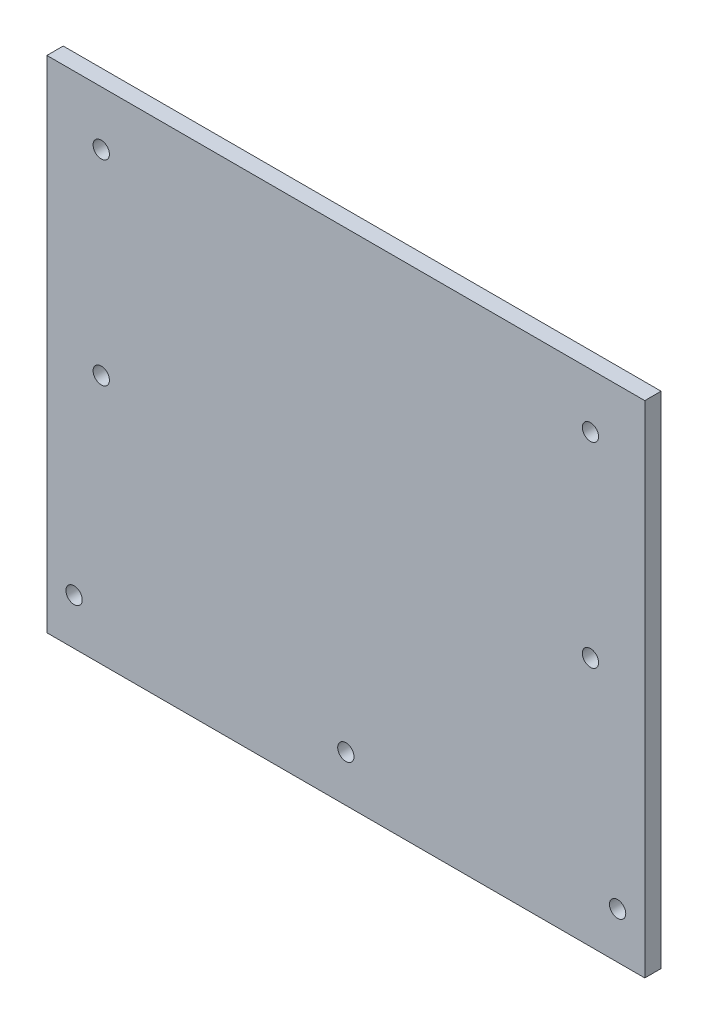
SolidWorks part; units mm, degrees
ref_plane "前视基准面" through (0, 0, 0) normal (0, 0, 1) x (1, 0, 0)
ref_plane "上视基准面" through (0, 0, 0) normal (0, 1, 0) x (1, 0, 0)
ref_plane "右视基准面" through (0, 0, 0) normal (1, 0, 0) x (0, 0, -1)
sketch "草图1" plane through (0, 0, 0) normal (0, 0, 1) x (1, 0, 0)
  line L1 (55, -46) -> (-55, -46)
  line L2 (55, -46) -> (55, 46)
  line L3 (55, 46) -> (-55, 46)
  line L4 (-55, -46) -> (-55, 46)
  line L5 (55, -46) -> (-55, 46) construction
  line L6 (55, 46) -> (-55, -46) construction
  point P0 (0, 0)
  dimension "D1" = 110
  dimension "D2" = 92
extrude "凸台-拉伸1" add sketch "草图1" along normal blind 3
sketch "草图2" plane through (0, 0, 3) normal (0, 0, 1) x (1, 0, 0)
  line L0 (-55, -46) -> (55, -46) construction
  line L1 (0, -46) -> (0, -37.5) construction
  line L2 (0, -37.5) -> (50, -37.5)
  line L3 (0, -37.5) -> (-50, -37.5)
  line L4 (-50, -37.5) -> (-16.0719, -37.5)
  circle A0 centre (0, -37.5) radius 1.5
  circle A1 centre (50, -37.5) radius 1.5
  circle A2 centre (-50, -37.5) radius 1.5
  dimension "D2" = 3
  dimension "D4" = 3
  dimension "D5" = 3
  dimension "D1" = 8.5
  dimension "D3" = 50
  dimension "D6" = 50
extrude "切除-拉伸1" cut sketch "草图2" against normal through all contours A2 | L2 A0 L3 | L1 A0 L2 | A0 L1 L3 | A1 region at (-0.6366, -38.1366, 3) region at (-51.4576, -37.5, 3) region at (50, -36.0424, 3) region at (0.6366, -38.1366, 3) region at (0, -36.8634, 3)
sketch "草图3" plane through (0, 0, 3) normal (0, 0, 1) x (1, 0, 0)
  line L0 (0, 46) -> (0, 30.213) construction
  line L1 (-55, 46) -> (-45, 46)
  line L2 (-55, 46) -> (-55, 36)
  line L3 (-55, 36) -> (-45, 36)
  line L4 (-45, 46) -> (-45, 36)
  line L5 (55, 46) -> (-55, 46) construction
  line L6 (45, 46) -> (45, 36)
  line L7 (55, 36) -> (45, 36)
  line L8 (55, 46) -> (55, 36)
  line L9 (55, 46) -> (45, 46)
  line L10 (-55, 0) -> (-45, 0)
  line L11 (-55, 46) -> (-55, -46) construction
  circle A0 centre (-45, 36) radius 1.5
  circle A1 centre (45, 36) radius 1.5
  circle A2 centre (-45, 0) radius 1.5
  circle A3 centre (45, 0) radius 1.5
  dimension "D3" = 3
  dimension "D4" = 3
  dimension "D1" = 10
  dimension "D2" = 10
  dimension "D5" = 10
extrude "切除-拉伸2" cut sketch "草图3" against normal through all contours L3 A0 L4 | L4 A0 L3 | A1 L7 L6 | A1 L6 L7 | A2 | A3 region at (-44.7878, 35.7878, 3) region at (-45.6366, 36.6366, 3) region at (45.6366, 36.6366, 3) region at (44.7878, 35.7878, 3) region at (-45, -1.4576, 3) region at (45, 0, 3)
